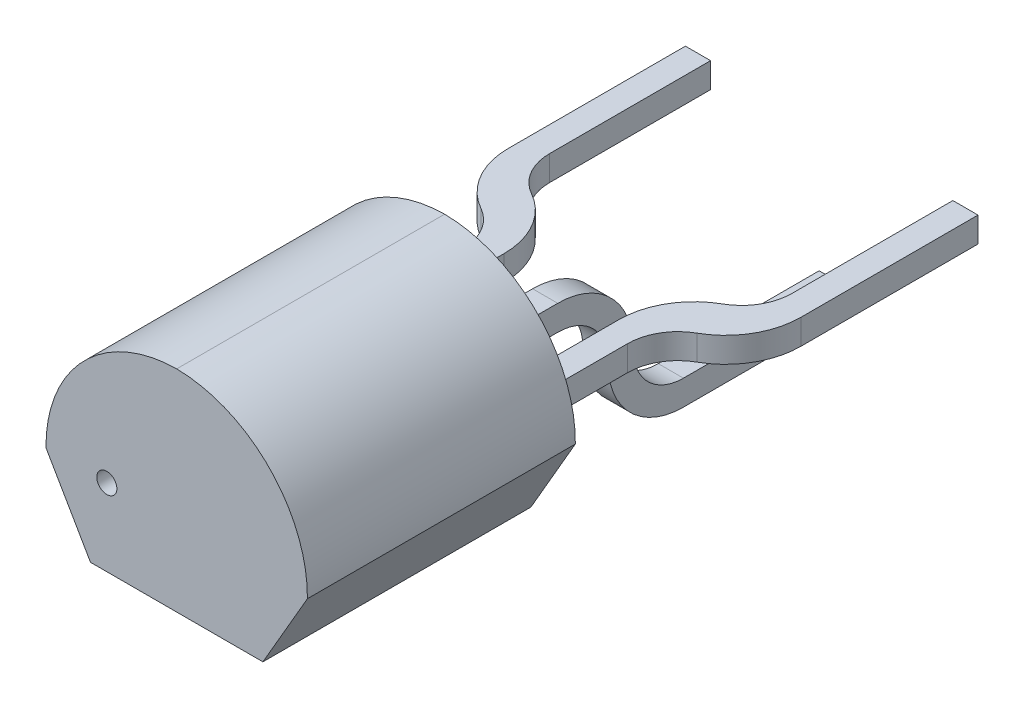
SolidWorks part; units mm, degrees
ref_plane "Спереди" through (0, 0, 0) normal (0, 0, 1) x (1, 0, 0)
ref_plane "Сверху" through (0, 0, 0) normal (0, 1, 0) x (1, 0, 0)
ref_plane "Справа" through (0, 0, 0) normal (1, 0, 0) x (0, 0, -1)
sketch "Эскиз1" plane through (0, 0, 0) normal (0, 0, 1) x (1, 0, 0)
  line L0 (1.14, 0.25) -> (1.64, 0.25)
  line L1 (-0.25, 0.25) -> (0.25, 0.25)
  line L2 (-0.25, 0.25) -> (-0.25, -0.25)
  line L3 (-0.25, -0.25) -> (0.25, -0.25)
  line L4 (0.25, 0.25) -> (0.25, -0.25)
  line L5 (1.14, 0.25) -> (1.14, -0.25)
  line L6 (1.14, -0.25) -> (1.64, -0.25)
  line L7 (1.64, 0.25) -> (1.64, -0.25)
  line L8 (2.53, 0.25) -> (3.03, 0.25)
  line L9 (2.53, 0.25) -> (2.53, -0.25)
  line L10 (2.53, -0.25) -> (3.03, -0.25)
  line L11 (3.03, 0.25) -> (3.03, -0.25)
  line L12 (1.39, 0.25) -> (1.39, -1.8309) construction
  dimension "D1" = 0.5
  dimension "D2" = 0.5
  dimension "D3" = 1.39
ref_plane "Плоскость1" through (0, 0, 2.54) normal (0, 0, 1) x (1, 0, 0)
sketch "Эскиз3" plane through (0, 0, 2.54) normal (0, 0, 1) x (1, 0, 0)
  line L0 (-0.325, -1.53) -> (3.105, -1.53)
  line L6 (-1.21, 0) -> (-0.325, -1.53)
  line L7 (3.99, 0) -> (3.105, -1.53)
  arc A0 (-1.21, 0) -> (1.39, 2.66) centre (1.42, 0.03) cw
  arc A1 (1.39, 2.66) -> (3.99, 0) centre (1.36, 0.03) cw
  dimension "D3" = 2.6302
  dimension "D4" = 2.6302
  dimension "D1" = 5.2
  dimension "D2" = 4.19
  dimension "D5" = 3.43
  dimension "D6" = 1.21
  dimension "D7" = 120.046
extrude "Вытянуть1" add sketch "Эскиз3" along normal blind 5.33
extrude "Вытянуть2" add sketch "Эскиз1" along normal blind 2.54
extrude "Вытянуть3" add sketch "Эскиз1<2>" against normal blind 10.16
sketch "Эскиз1<2>" plane through (0, 0, 0) normal (0, 0, 1) x (1, 0, 0) same geometry as "Эскиз1"
sketch "Эскиз4" plane through (0, 0, 7.87) normal (0, 0, 1) x (1, 0, 0)
  circle A0 centre (0, 0) radius 0.2
extrude "Вырез-Вытянуть1" cut sketch "Эскиз4" against normal blind 0.5
sketch "Эскиз5" plane through (3.03, 0, 0) normal (1, 0, 0) x (0, 0, -1)
  line L0 (0.46, 0.25) -> (0.46, -0.25)
  line L4 (-2.54, -0.25) -> (10.16, -0.25)
  line L5 (10.16, -0.25) -> (10.16, 0.25)
  line L6 (10.16, 0.25) -> (-2.54, 0.25)
  line L7 (-2.54, 0.25) -> (-2.54, -0.25)
  line L8 (0.46, -0.25) -> (10.16, -0.25)
  line L9 (10.16, -0.25) -> (10.16, 0.25)
  line L10 (10.16, 0.25) -> (0.46, 0.25)
  dimension "D1" = 0
extrude "Вытянуть4" add sketch "Эскиз5" along normal blind 1.27
sketch "Эскиз6" plane through (-0.25, 0, 0) normal (-1, 0, 0) x (0, 0, 1)
  line L4 (-10.16, 0.25) -> (-10.16, -0.25)
  line L5 (-0.46, 0.25) -> (-10.16, 0.25)
  line L6 (-0.46, -0.25) -> (-0.46, 0.25)
  line L7 (-10.16, -0.25) -> (-0.46, -0.25)
  line L8 (-10.16, 0.25) -> (-10.16, -0.25)
  line L9 (-0.46, 0.25) -> (-10.16, 0.25)
  line L10 (-0.46, -0.25) -> (-0.46, 0.25)
  line L11 (-10.16, -0.25) -> (-0.46, -0.25)
  dimension "D1" = 0
extrude "Вытянуть5" add sketch "Эскиз6" along normal blind 1.27
sketch "Эскиз7" plane through (0, -0.25, 0) normal (0, 1, 0) x (1, 0, 0)
  line L0 (1.14, 0.46) -> (1.64, 0.46)
  line L4 (1.64, -2.54) -> (1.64, 10.16)
  line L5 (1.64, 10.16) -> (1.14, 10.16)
  line L6 (1.14, 10.16) -> (1.14, -2.54)
  line L7 (1.14, -2.54) -> (1.64, -2.54)
  line L8 (1.64, 0.46) -> (1.64, 10.16)
  line L9 (1.64, 10.16) -> (1.14, 10.16)
  line L10 (1.14, 10.16) -> (1.14, 0.46)
  dimension "D1" = 0
extrude "Вытянуть6" add sketch "Эскиз7" against normal blind 2.54
sketch "Эскиз8" plane through (0, -0.25, 0) normal (0, -1, 0) x (1, 0, 0)
  line L0 (-1.52, -10.16) -> (-1.52, -0.46) construction
  line L1 (-1.02, -10.7756) -> (0.3527, -10.7756)
  line L2 (-1.02, -10.7756) -> (-1.02, -0.96)
  line L3 (-1.02, -0.96) -> (0.3527, -0.96)
  line L4 (0.3527, -10.7756) -> (0.3527, -0.96)
  line L5 (-1.52, -0.46) -> (-0.25, -0.46) construction
  line L6 (1.39, -8.0301) -> (1.39, -4.6197) construction
  line L7 (1.14, -10.16) -> (1.14, -0.46) construction
  line L8 (1.64, -0.46) -> (1.64, -10.16) construction
  line L9 (2.4273, -10.7756) -> (2.4273, -0.96)
  line L10 (3.8, -0.96) -> (2.4273, -0.96)
  line L11 (3.8, -10.7756) -> (3.8, -0.96)
  line L12 (3.8, -10.7756) -> (2.4273, -10.7756)
  dimension "D1" = 0.5
  dimension "D2" = 0.5
extrude "Вырез-Вытянуть2" cut sketch "Эскиз8" against normal blind 2.54
sketch "Эскиз9" plane through (1.64, 0, 0) normal (1, 0, 0) x (0, 0, -1)
  line L0 (0.46, -2.79) -> (0.46, -0.25) construction
  line L1 (10.4824, -2.29) -> (0.96, -2.29)
  line L2 (10.4824, -2.29) -> (10.4824, 1.3478)
  line L3 (10.4824, 1.3478) -> (0.96, 1.3478)
  line L4 (0.96, -2.29) -> (0.96, 1.3478)
  line L5 (0.46, -2.79) -> (10.16, -2.79) construction
  dimension "D1" = 0.5
  dimension "D2" = 0.5
extrude "Вырез-Вытянуть3" cut sketch "Эскиз9" against normal blind 1
fillet "Скругление1" radius 1 6 edges at (-1.02, 0, -0.96) (1.39, -2.29, -0.96) (3.8, 0, -0.96) (3.03, 0, -0.46) (1.39, -0.25, -0.46) (-0.25, 0, -0.46)
fillet "Скругление2" radius 1.5 6 edges at (-1.52, 0, -0.46) (1.39, -2.79, -0.46) (4.3, 0, -0.46) (0.25, 0, -0.96) (1.39, 0.25, -0.96) (2.53, 0, -0.96)
sketch "Эскиз10" plane through (0, 0, -10.16) normal (0, 0, -1) x (-1, 0, 0)
  line L4 (-1.14, -2.79) -> (-1.14, -2.29)
  line L5 (-1.14, -2.29) -> (-1.64, -2.29)
  line L6 (-1.64, -2.29) -> (-1.64, -2.79)
  line L7 (-1.64, -2.79) -> (-1.14, -2.79)
  line L8 (-1.14, -2.79) -> (-1.14, -2.29)
  line L9 (-1.14, -2.29) -> (-1.64, -2.29)
  line L10 (-1.64, -2.29) -> (-1.64, -2.79)
  line L11 (-1.64, -2.79) -> (-1.14, -2.79)
  line L12 (1.52, 0.25) -> (1.02, 0.25)
  line L13 (1.02, 0.25) -> (1.02, -0.25)
  line L14 (1.02, -0.25) -> (1.52, -0.25)
  line L15 (1.52, -0.25) -> (1.52, 0.25)
  line L16 (1.52, 0.25) -> (1.02, 0.25)
  line L17 (1.02, 0.25) -> (1.02, -0.25)
  line L18 (1.02, -0.25) -> (1.52, -0.25)
  line L19 (1.52, -0.25) -> (1.52, 0.25)
  line L20 (-4.3, -0.25) -> (-3.8, -0.25)
  line L21 (-3.8, -0.25) -> (-3.8, 0.25)
  line L22 (-3.8, 0.25) -> (-4.3, 0.25)
  line L23 (-4.3, 0.25) -> (-4.3, -0.25)
  line L24 (-4.3, -0.25) -> (-3.8, -0.25)
  line L25 (-3.8, -0.25) -> (-3.8, 0.25)
  line L26 (-3.8, 0.25) -> (-4.3, 0.25)
  line L27 (-4.3, 0.25) -> (-4.3, -0.25)
  dimension "D1" = 0
  dimension "D2" = 0
  dimension "D3" = 0
extrude "Вырез-Вытянуть4" cut sketch "Эскиз10" against normal blind 5
sketch "Эскиз11" plane through (0, 0, -5.16) normal (0, 0, -1) x (-1, 0, 0)
  line L0 (-1.14, -2.29) -> (-1.64, -2.29) construction
  line L1 (-1.14, -2.79) -> (-1.14, -2.29) construction
  circle A0 centre (-1.39, -2.54) radius 0.147
  dimension "D1" = 0.25
  dimension "D2" = 0.25
extrude "Вырез-Вытянуть5" cut sketch "Эскиз11" against normal blind 2
